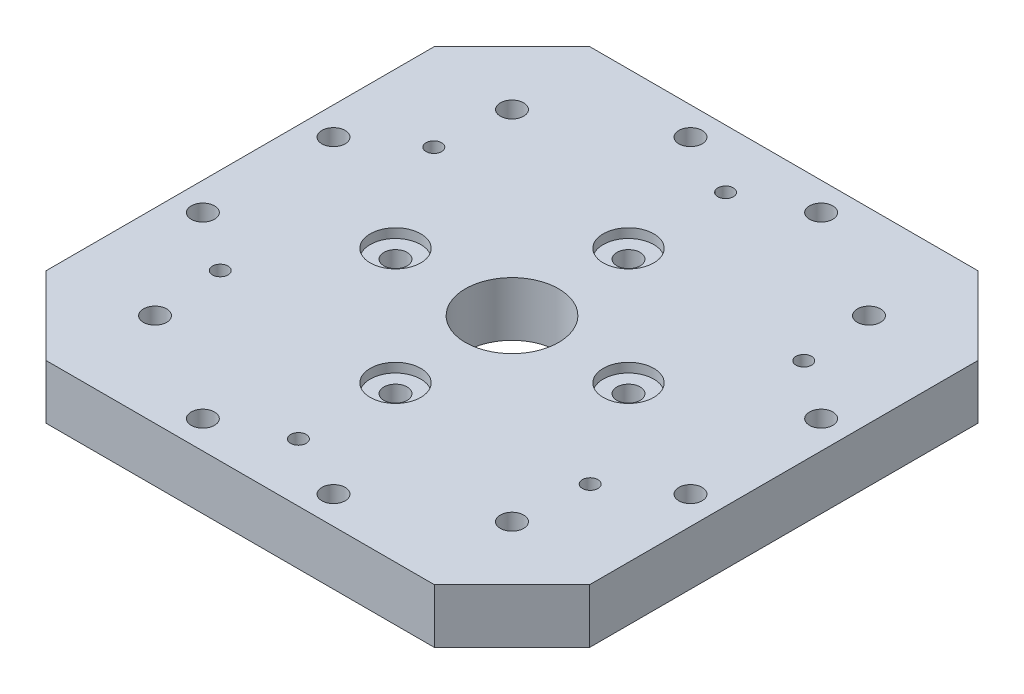
SolidWorks part; units mm, degrees
ref_plane "Front Plane" through (0, 0, 0) normal (0, 0, 1) x (1, 0, 0)
ref_plane "Top Plane" through (0, 0, 0) normal (0, 1, 0) x (1, 0, 0)
ref_plane "Right Plane" through (0, 0, 0) normal (1, 0, 0) x (0, 0, -1)
sketch "Sketch1" plane through (0, 0, 0) normal (0, 1, 0) x (1, 0, 0)
  line L0 (-49.4318, 0) -> (0, 0) construction
  line L1 (0, 0) -> (-47.2333, -12.6561) construction
  line L2 (-35, 35) -> (35, 35)
  line L3 (-35, 35) -> (-35, -35)
  line L4 (35, 35) -> (35, -35)
  line L5 (-35, -35) -> (35, -35)
  circle A0 centre (0, 0) radius 35 construction
  circle A1 centre (0, 0) radius 27.5 construction
  circle A2 centre (0, 0) radius 6
  circle A3 centre (0, 0) radius 15 construction
  circle A4 centre (0, 15) radius 1.5
  circle A5 centre (15, 0) radius 1.5
  circle A6 centre (0, -15) radius 1.5
  circle A7 centre (-15, 0) radius 1.5
  circle A11 centre (0, 0) radius 32.5 construction
  circle A12 centre (-31.3926, -8.4116) radius 1.5
  circle A13 centre (-31.3926, 8.4116) radius 1.5
  circle A14 centre (-22.981, 22.981) radius 1.5
  circle A15 centre (-8.4116, 31.3926) radius 1.5
  circle A16 centre (8.4116, 31.3926) radius 1.5
  circle A17 centre (22.981, 22.981) radius 1.5
  circle A18 centre (31.3926, 8.4116) radius 1.5
  circle A19 centre (31.3926, -8.4116) radius 1.5
  circle A20 centre (22.981, -22.981) radius 1.5
  circle A21 centre (8.4116, -31.3926) radius 1.5
  circle A22 centre (-8.4116, -31.3926) radius 1.5
  circle A23 centre (-22.981, -22.981) radius 1.5
  circle A24 centre (0, 27.5) radius 1
  circle A25 centre (23.8157, 13.75) radius 1
  circle A26 centre (23.8157, -13.75) radius 1
  circle A27 centre (0, -27.5) radius 1
  circle A28 centre (-23.8157, -13.75) radius 1
  circle A29 centre (-23.8157, 13.75) radius 1
  point P17 (0, 0)
  point P44 (0, 0)
  point P46 (0, 0)
  point P57 (0, 0)
  dimension "D1" = 70
  dimension "D2" = 55
  dimension "D3" = 12
  dimension "D4" = 3
  dimension "D6" = 30
  dimension "D7" = 65
  dimension "D9" = 3
  dimension "D11" = 2
  dimension "D8" = 15
  dimension "D5" = 4
  dimension "D10" = 12
  dimension "D12" = 6
extrude "Boss-Extrude1" add sketch "Sketch1" along normal blind 7
sketch "Sketch2" plane through (0, 7, 0) normal (0, 1, 0) x (1, 0, 0)
  circle A0 centre (0, 0) radius 15 construction
  circle A1 centre (0, 15) radius 3.25
  circle A2 centre (15, 0) radius 3.25
  circle A3 centre (0, -15) radius 3.25
  circle A4 centre (-15, 0) radius 3.25
  point P15 (0, 0)
  dimension "D1" = 6.5
  dimension "D2" = 4
extrude "Cut-Extrude1" cut sketch "Sketch2" against normal blind 1.2
chamfer "Chamfer1" distance 10 angle 45 4 edges at (-35, 3.5, -35) (35, 3.5, -35) (35, 3.5, 35) (-35, 3.5, 35)
